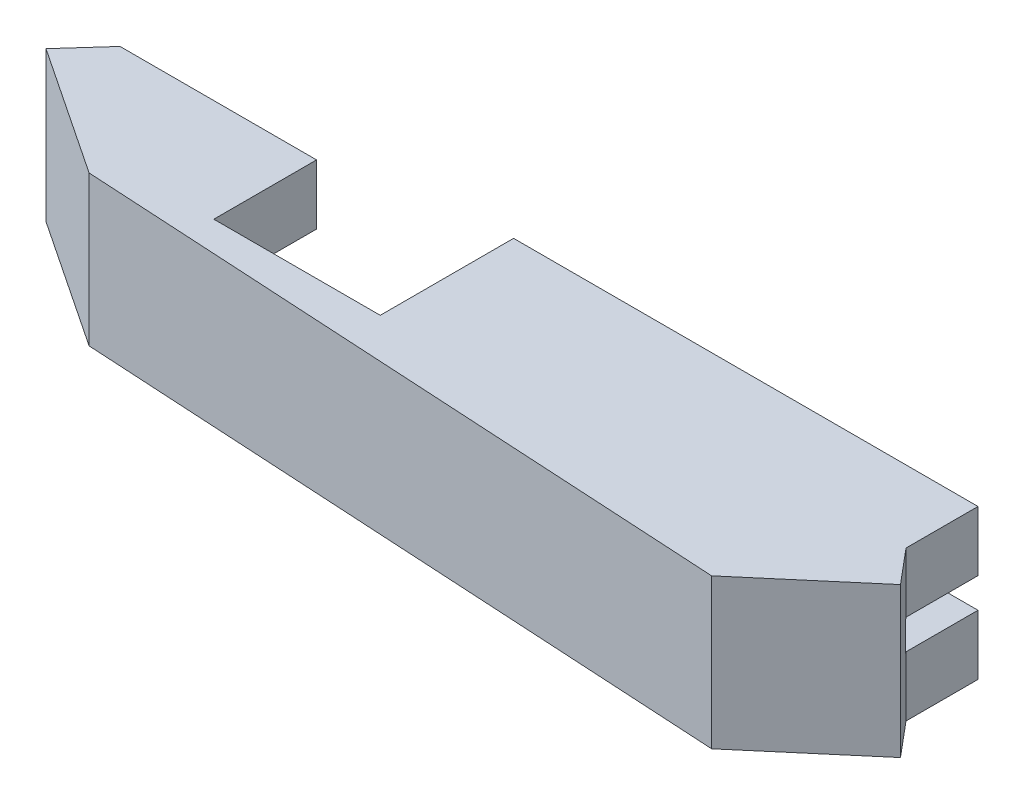
SolidWorks part; units mm, degrees
ref_plane "Front Plane" through (0, 0, 0) normal (0, 0, 1) x (1, 0, 0)
ref_plane "Top Plane" through (0, 0, 0) normal (0, 1, 0) x (1, 0, 0)
ref_plane "Right Plane" through (0, 0, 0) normal (1, 0, 0) x (0, 0, -1)
sketch "Sketch2" plane through (0, 0, 0) normal (0, 1, 0) x (1, 0, 0)
  line L0 (0, 0) -> (24.11, 0)
  line L1 (0, 0) -> (-7.6172, 6.8586)
  line L2 (24.11, 0) -> (34.41, 0)
  line L3 (29.26, 0) -> (29.26, 4.5)
  line L4 (29.26, 0) -> (29.26, 4.5)
  line L5 (29.26, 0) -> (29.26, -0.65)
  line L6 (34.41, 0) -> (42.73, 0)
  line L7 (42.73, 0) -> (47.61, 4.0948)
  line L8 (-7.6172, 6.8586) -> (5.5, 6.8586)
  line L9 (24.1512, 0) -> (16.61, 0)
  line L10 (16.61, 0) -> (16.61, 8.9)
  line L11 (16.61, 8.9) -> (47.61, 8.9)
  line L12 (47.61, 8.9) -> (47.61, 4.0948)
  line L13 (0, 0) -> (5.5, 0)
  line L14 (5.5, 0) -> (5.5, 6.8586)
  line L15 (0, 0) -> (-0.2007, -0.2229)
  line L16 (-7.6172, 6.8586) -> (-9.9592, 4.2576)
  line L17 (-9.9592, 4.2576) -> (-1.3383, -1.4863)
  line L18 (42.73, 0) -> (42.73, -0.3)
  line L19 (-1.3383, -1.4863) -> (42.73, -4)
  line L20 (47.61, 4.0948) -> (49.5384, 1.7967)
  line L21 (42.73, -4) -> (49.5384, 1.7967)
  line L22 (-7.6172, 6.8586) -> (-7.818, 6.6356)
  line L23 (-7.818, 6.6356) -> (-0.1152, -0.3)
  line L24 (0.2977, -0.6717) -> (0.2766, -0.6489)
  line L25 (29.26, 4.5) -> (29.26, 4.2)
  line L26 (42.73, 0) -> (42.73, -0.3)
  line L27 (42.73, -0.3) -> (-0.1152, -0.3)
  line L28 (-0.2701, -0.3) -> (-1.3383, -1.4863)
  line L29 (34.3688, -0.3) -> (34.1688, -0.3)
  line L30 (34.1688, -0.3) -> (34.1688, 0.6076)
  line L31 (24.1512, -0.3) -> (24.3512, -0.3)
  line L32 (24.3512, -0.3) -> (24.3512, 0.6076)
  line L33 (47.61, 4.0948) -> (47.8028, 3.865)
  line L34 (47.8028, 3.865) -> (42.8392, -0.3)
  line L35 (42.73, -0.3) -> (42.8392, -0.3)
  arc A0 (34.3688, 0) -> (24.1512, 0) centre (29.26, -0.65) ccw
  arc A1 (34.3688, -0.3) -> (24.1512, -0.3) centre (29.26, -0.95) ccw
  dimension "D1" = 24.11
  dimension "D2" = 10.25
  dimension "D3" = 138
  dimension "D4" = 10.3
  dimension "D5" = 4.5
  dimension "D6" = 0.65
  dimension "D7" = 8.32
  dimension "D8" = 140
  dimension "D9" = 7.5
  dimension "D10" = 8.9
  dimension "D11" = 31
  dimension "D12" = 5.5
  dimension "D13" = 90
  dimension "D14" = 2
  dimension "D15" = 90
  dimension "D16" = 3.5
  dimension "D17" = 4
  dimension "D18" = 3
  dimension "D19" = 90
  dimension "D20" = 0.3
  dimension "D21" = 0.3
  dimension "D22" = 0.2
  dimension "D23" = 0.2
  dimension "D24" = 0.3
extrude "Boss-Extrude2" add sketch "Sketch2" along normal blind 4 contours A0 L2 L6 L7 L12 L11 L10 L0 | L0 L14 L8 L1 | A1 L2 L0 L15 L23 L27 | A1 L2 A0 L4 | A1 L4 A0 L2 | L3 A1 L32 L2 | L30 A1 L3 L2 | L32 L27 L5 L2 | L27 L30 L2 L5 | L2 A1 L30 | L27 A1 L2 L30 | A1 L27 L18 L6 L2 | L35 L27 L23 L16 L17 L19 L21 L20 L34 | L32 A1 L2 | L2 A1 L27 L32 | L18 L35 L34 L20 L7 | L16 L23 L15 L1 region at (0.586, 0, -3.897) region at (-3.909, 0, -3.3178) region at (12.029, 0, 0.1501) region at (22.6521, 0, 0.6792) region at (31.9415, 0, -4.9712) region at (24.2617, 0, 0.1566) region at (25.901, 0, -3.1635) region at (26.8056, 0, 0.15) region at (24.2979, 0, -0.2106) region at (32.619, 0, -3.1635) region at (45.2248, 0, -1.8968) region at (31.7144, 0, 0.15) region at (27.1976, 0, -1.7623) region at (31.3224, 0, -1.7623) region at (38.5384, 0, 0.1499) region at (34.2583, 0, 0.1566) region at (34.2221, 0, -0.2106)
extrude "Boss-Extrude3" add sketch "Sketch2<9>" against normal blind 2 contours L35 L27 L23 L16 L17 L19 L21 L20 L34 | L3 A1 L32 L2 | L30 A1 L3 L2 | L27 L30 L2 L5 | L32 L27 L5 L2 region at (22.6521, 0, 0.6792) region at (26.8056, 0, 0.15) region at (31.7144, 0, 0.15) region at (27.1976, 0, -1.7623) region at (31.3224, 0, -1.7623)
sketch "Sketch2<9>" plane through (0, 0, 0) normal (0, 1, 0) x (1, 0, 0) same geometry as "Sketch2"
ref_plane "Plane2" through (0, -2, 0) normal (0, -1, 0) x (-1, 0, 0)
sketch "Sketch4" plane through (0, -2, 0) normal (0, -1, 0) x (-1, 0, 0)
  line L0 (0, 0) -> (0, 6.8586)
  line L2 (0, 6.8586) -> (7.6172, 6.8586)
  line L9 (-24.1512, 0) -> (-24.1512, 8.9)
  line L36 (-49.5384, 1.7967) -> (-48.2219, 0.6759)
  line L37 (-42.73, -4) -> (-49.5384, 1.7967) construction
  line L39 (-42.73, -0.3) -> (-42.8392, -0.3)
  line L40 (-47.8028, 3.865) -> (-42.8392, -0.3)
  line L41 (-47.61, 4.0948) -> (-47.8028, 3.865)
  line L43 (-24.1512, -0.3) -> (-24.3512, -0.3)
  line L44 (-34.1688, -0.3) -> (-34.1688, 0.6076)
  line L45 (-34.3688, -0.3) -> (-34.1688, -0.3)
  line L46 (0.2701, -0.3) -> (1.3383, -1.4863)
  line L47 (-42.73, -0.3) -> (0.1152, -0.3)
  line L48 (-42.73, 0) -> (-42.73, -0.3)
  line L49 (-29.26, 4.5) -> (-29.26, 4.2)
  line L50 (-0.2977, -0.6717) -> (-0.2766, -0.6489)
  line L51 (7.818, 6.6356) -> (0.1152, -0.3)
  line L52 (7.6172, 6.8586) -> (7.818, 6.6356)
  line L53 (-42.73, -4) -> (-49.5384, 1.7967)
  line L54 (-47.61, 4.0948) -> (-49.5384, 1.7967)
  line L55 (1.3383, -1.4863) -> (-42.73, -4)
  line L56 (-42.73, 0) -> (-42.73, -0.3)
  line L57 (9.9592, 4.2576) -> (1.3383, -1.4863)
  line L58 (7.6172, 6.8586) -> (9.9592, 4.2576)
  line L59 (0, 0) -> (0.2007, -0.2229)
  line L60 (-5.5, 0) -> (-5.5, 6.8586)
  line L61 (0, 0) -> (-5.5, 0)
  line L62 (-47.61, 8.9) -> (-47.61, 4.0948)
  line L63 (-16.61, 8.9) -> (-47.61, 8.9)
  line L64 (-16.61, 0) -> (-16.61, 8.9)
  line L65 (-24.1512, 0) -> (-16.61, 0)
  line L66 (7.6172, 6.8586) -> (-5.5, 6.8586)
  line L67 (-42.73, 0) -> (-47.61, 4.0948)
  line L68 (-34.41, 0) -> (-42.73, 0)
  line L69 (-29.26, 0) -> (-29.26, -0.65)
  line L70 (-29.26, 0) -> (-29.26, 4.5)
  line L71 (-29.26, 0) -> (-29.26, 4.5)
  line L72 (-24.11, 0) -> (-34.41, 0)
  line L73 (0, 0) -> (7.6172, 6.8586)
  line L74 (0, 0) -> (-24.11, 0)
  arc A2 (-34.3688, -0.3) -> (-24.1512, -0.3) centre (-29.26, -0.95) cw
  arc A3 (-34.3688, 0) -> (-24.1512, 0) centre (-29.26, -0.65) cw
extrude "Boss-Extrude4" add sketch "Sketch4" along normal blind 4 contours L0 L73 L2 | A3 L9 L63 L62 L67 L68 L72 | A2 L70 L72 | A2 L44 L72 L70 | A3 L72 A2 L49 | A3 L49 A2 L72 | A2 L72 L69 L47 L43 | L69 L72 L44 L47 | L58 L51 L47 L43 L45 L39 L40 L54 L36 L53 L55 L57 | L47 A2 L72 L68 L48 | L48 L67 L41 L40 L39 | A2 L72 L44 | A2 L45 L44 L72 | L72 A2 L47 L51 L59 L61 L74 L65 | L73 L59 L51 L52 region at (-3.909, -2, -3.3178) region at (12.029, -2, 0.1501) region at (-2.5391, -2, -4.5724) region at (22.6521, -2, 0.6792) region at (26.7166, -2, 0.1502) region at (25.9279, -2, -3.0657) region at (27.1884, -2, -1.7574) region at (36.6783, -2, -5.1847) region at (31.7144, -2, 0.15) region at (31.3224, -2, -1.7623) region at (32.3417, -2, -3.2609) region at (34.2583, -2, 0.1566) region at (34.2221, -2, -0.2106) region at (45.2248, -2, -1.8968) region at (38.5384, -2, 0.1499)
